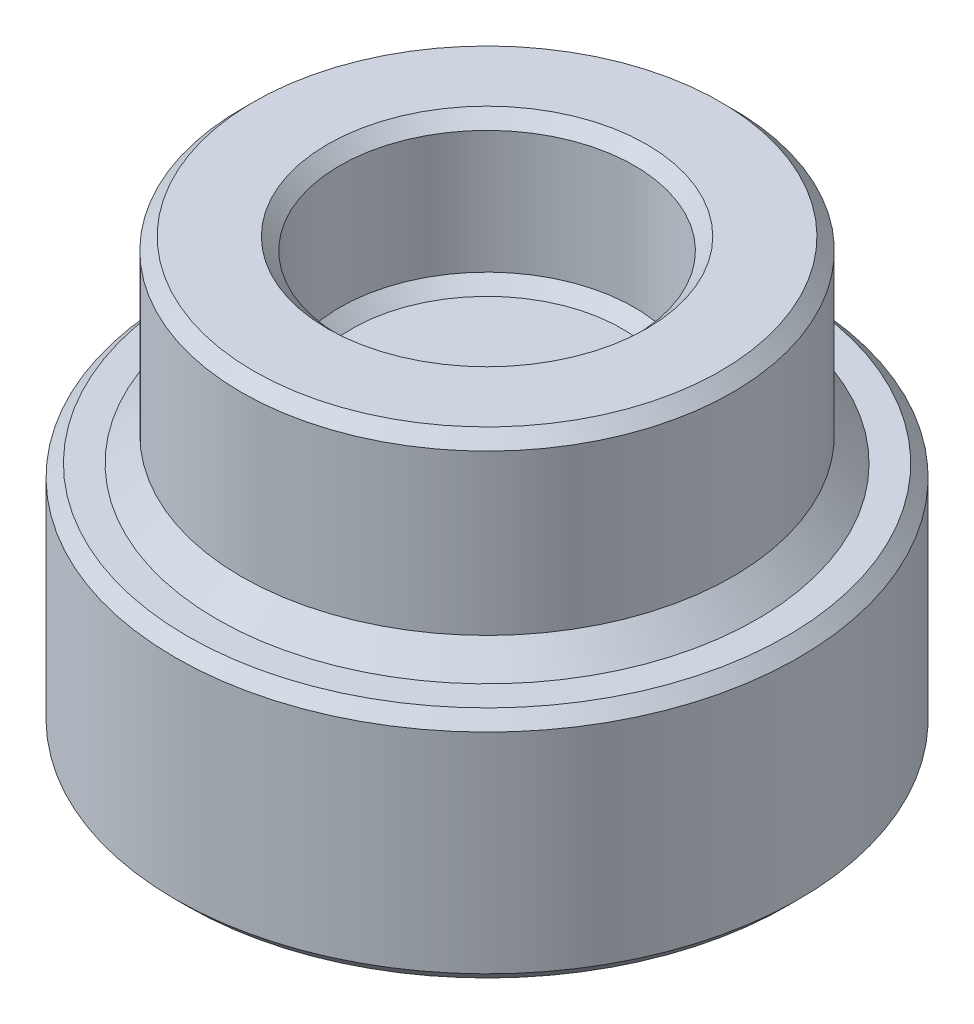
SolidWorks part; units mm, degrees
note: '?' marks a value the reader was unsure of. The reader was unsure of these and kept them because the rebuilt part matched: shared geometry of "Sketch1<3>".
material "ABS"
ref_plane "Front Plane" through (0, 0, 0) normal (0, 0, 1) x (1, 0, 0)
ref_plane "Top Plane" through (0, 0, 0) normal (0, 1, 0) x (1, 0, 0)
ref_plane "Right Plane" through (0, 0, 0) normal (1, 0, 0) x (0, 0, -1)
ref_axis "X Axis" through (88.99, 0, 0) along (-1, 0, 0)?
ref_axis "Y Axis" through (0, 55, 0) along (0, -1, 0)?
ref_axis "Z Axis" through (0, 0, -88.99) along (0, 0, 1)?
sketch "Sketch1" plane through (0, 0, 0) normal (0, 1, 0) x (1, 0, 0)
  circle A0 centre (0, 0) radius 5
  circle A1 centre (0, 0) radius 3
  dimension "D1" = 6
  dimension "D2" = 10
extrude "Boss-Extrude1" add sketch "Sketch1" along normal blind 1 contours A1 | A0 A1
extrude "Boss-Extrude2" add sketch "Sketch1<3>" along normal blind 4
sketch "Sketch1<3>" plane through (0, 0, 0) normal (0, 1, 0) x (1, 0, 0) same geometry as "Sketch1"
chamfer "Chamfer1" distance 0.25 angle 45 3 edges at (0, 4, 3) (0, 4, 5) (0, 1, 3)
sketch "Sketch5" plane through (0, 0, 0) normal (0, 1, 0) x (1, 0, 0)
  circle A0 centre (0, 0) radius 6.35
  dimension "D1" = 12.7
extrude "Boss-Extrude4" add sketch "Sketch5" against normal blind 4.7625
sketch "Sketch4" plane through (0, -4.7625, 0) normal (0, -1, 0) x (-1, 0, 0)
  point P0 (0, 0)
hole_wizard "3/8 (0.375) Diameter Hole1" [suppressed] positions "Sketch4" profile "Sketch3" hole size "3/8" standard "ANSI Inch"
sketch "Sketch3" plane through (0, -12.5, 0) normal (1, 0, 0) x (0, 0, -1)
  line L0 (0, 0) -> (0, 12.5)
  line L1 (0, 12.5) -> (4.7625, 12.0833)
  line L2 (4.7625, 12.0833) -> (4.7625, 0.635)
  line L3 (4.7625, 0.635) -> (5.3975, 0)
  line L5 (5.3975, 0) -> (0, 0)
  line L6 (-4.7625, 0.635) -> (-5.3975, 0) construction
  line L10 (0, 12.5) -> (-4.7625, 12.0833) construction
  line L11 (0, -6.35) -> (0, 107.95) construction
  dimension "Hole Dia." = 9.525
  dimension "Hole Depth" = 12.5
  dimension "Near C'Sink Dia." = 10.795
  dimension "Near C'Sink Angle" = 90
  dimension "Drill Angle" = 170
sketch "Sketch8" plane through (0, -4.7625, 0) normal (0, -1, 0) x (-1, 0, 0)
  point P0 (0, 0)
hole_wizard "Ø3.5 (3.5) Diameter Hole1" positions "Sketch8" profile "Sketch7" hole size "Ø3.5" standard "ANSI Metric"
sketch "Sketch7" plane through (0, -4.7625, 0) normal (1, 0, 0) x (0, 0, -1)
  line L0 (0, 0) -> (0, 4.76)
  line L1 (0, 4.76) -> (1.75, 4.4514)
  line L2 (1.75, 4.4514) -> (1.75, 0.25)
  line L3 (1.75, 0.25) -> (2, 0)
  line L5 (2, 0) -> (0, 0)
  line L6 (-1.75, 0.25) -> (-2, 0) construction
  line L10 (0, 4.76) -> (-1.75, 4.4514) construction
  line L11 (0, -6.35) -> (0, 107.95) construction
  dimension "Hole Dia." = 3.5
  dimension "Hole Depth" = 4.76
  dimension "Near C'Sink Dia." = 4
  dimension "Near C'Sink Angle" = 90
  dimension "Drill Angle" = 160
sketch "Sketch11" [suppressed] plane through (0, -4, 0) normal (0, -1, 0) x (-1, 0, 0)
  point P0 (0, 0)
hole_wizard "Ø6.0mm Dowel Hole1" [suppressed] positions "Sketch11" profile "Sketch10" hole size "Ø6.0" standard "ANSI Metric"
sketch "Sketch10" plane through (0, -4, 0) normal (1, 0, 0) x (0, 0, -1)
  line L0 (0, 0) -> (0, 4)
  line L1 (0, 4) -> (3, 3.7375)
  line L2 (3, 3.7375) -> (3, 0.125)
  line L3 (3, 0.125) -> (3.125, 0)
  line L5 (3.125, 0) -> (0, 0)
  line L6 (-3, 0.125) -> (-3.125, 0) construction
  line L10 (0, 4) -> (-3, 3.7375) construction
  line L11 (0, -6.35) -> (0, 107.95) construction
  dimension "Hole Dia." = 6
  dimension "Hole Depth" = 4
  dimension "Near C'Sink Dia." = 6.25
  dimension "Near C'Sink Angle" = 90
  dimension "Drill Angle" = 170
chamfer "Chamfer2" distance 0.25 angle 45 2 edges at (0, -4.7625, 6.35) (0, 0, 6.35)
chamfer "Chamfer3" distance 0.5 angle 45 1 edges at (0, 0, 5)
